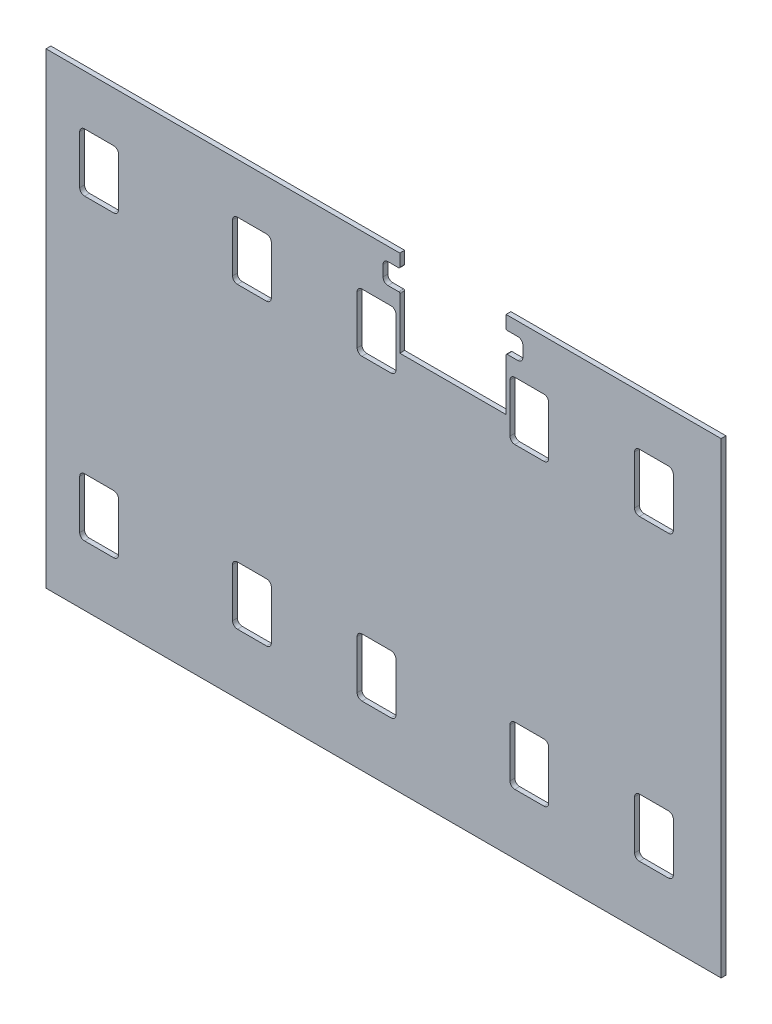
SolidWorks part; units mm, degrees
material "PP Film"
ref_plane "X-Y Datum" through (0, 0, 0) normal (0, 0, 1) x (1, 0, 0)
ref_plane "X-Z Datum" through (0, 0, 0) normal (0, 1, 0) x (1, 0, 0)
ref_plane "Y-Z Datum" through (0, 0, 0) normal (1, 0, 0) x (0, 0, -1)
sketch "Sketch1" plane through (0, 0, 0) normal (0, 0, 1) x (1, 0, 0)
  line L48 (-220.9897, 149.5877) -> (-220.9897, -156.2291)
  line L49 (-220.9897, -156.2291) -> (220.9897, -156.2291)
  line L50 (220.9897, -156.2291) -> (220.9897, 149.5877)
  line L51 (220.9897, 149.5877) -> (-220.9897, 149.5877)
extrude "Boss-Extrude1" add sketch "Sketch1" along normal blind 3.175 contours L50 L51 L48 L49 region at (0, -3.3207, 0)
sketch "Sketch2" plane through (0, 0, 3.175) normal (0, 0, 1) x (1, 0, 0)
  line L0 (-195.7605, 116.8) -> (-176.7105, 116.8) construction
  line L1 (-198.9355, 113.625) -> (-198.9355, 81.875) construction
  line L2 (-195.7605, 78.7) -> (-176.7105, 78.7) construction
  line L3 (-173.5355, 113.625) -> (-173.5355, 81.875) construction
  line L8 (-195.7605, 116.8) -> (-176.7105, 116.8)
  line L9 (-198.9355, 113.625) -> (-198.9355, 81.875)
  line L10 (-195.7605, 78.7) -> (-176.7105, 78.7)
  line L11 (-173.5355, 113.625) -> (-173.5355, 81.875)
  line L16 (-195.7605, -78.7) -> (-176.7105, -78.7) construction
  line L17 (-173.5355, -81.875) -> (-173.5355, -113.625) construction
  line L18 (-198.9355, -81.875) -> (-198.9355, -113.625) construction
  line L19 (-195.7605, -116.8) -> (-176.7105, -116.8) construction
  line L24 (-195.7605, -78.7) -> (-176.7105, -78.7)
  line L25 (-173.5355, -81.875) -> (-173.5355, -113.625)
  line L26 (-198.9355, -81.875) -> (-198.9355, -113.625)
  line L27 (-195.7605, -116.8) -> (-176.7105, -116.8)
  line L32 (-76.6655, -78.7) -> (-95.7155, -78.7) construction
  line L33 (-98.8905, -81.875) -> (-98.8905, -113.625) construction
  line L34 (-73.4905, -113.625) -> (-73.4905, -81.875) construction
  line L35 (-95.7155, -116.8) -> (-76.6655, -116.8) construction
  line L36 (-76.6655, -78.7) -> (-95.7155, -78.7)
  line L37 (-98.8905, -81.875) -> (-98.8905, -113.625)
  line L38 (-73.4905, -113.625) -> (-73.4905, -81.875)
  line L39 (-95.7155, -116.8) -> (-76.6655, -116.8)
  line L40 (-76.6655, 116.8) -> (-95.7155, 116.8) construction
  line L41 (-73.4905, 81.875) -> (-73.4905, 113.625) construction
  line L42 (-98.8905, 113.625) -> (-98.8905, 81.875) construction
  line L43 (-95.7155, 78.7) -> (-76.6655, 78.7) construction
  line L44 (-76.6655, 116.8) -> (-95.7155, 116.8)
  line L45 (-73.4905, 81.875) -> (-73.4905, 113.625)
  line L46 (-98.8905, 113.625) -> (-98.8905, 81.875)
  line L47 (-95.7155, 78.7) -> (-76.6655, 78.7)
  arc A0 (-173.5355, 113.625) -> (-176.7105, 116.8) centre (-176.7105, 113.625) ccw construction
  arc A1 (-195.7605, 116.8) -> (-198.9355, 113.625) centre (-195.7605, 113.625) ccw construction
  arc A2 (-198.9355, 81.875) -> (-195.7605, 78.7) centre (-195.7605, 81.875) ccw construction
  arc A3 (-176.7105, 78.7) -> (-173.5355, 81.875) centre (-176.7105, 81.875) ccw construction
  arc A8 (-173.5355, 113.625) -> (-176.7105, 116.8) centre (-176.7105, 113.625) ccw
  arc A9 (-195.7605, 116.8) -> (-198.9355, 113.625) centre (-195.7605, 113.625) ccw
  arc A10 (-198.9355, 81.875) -> (-195.7605, 78.7) centre (-195.7605, 81.875) ccw
  arc A11 (-176.7105, 78.7) -> (-173.5355, 81.875) centre (-176.7105, 81.875) ccw
  arc A16 (-195.7605, -78.7) -> (-198.9355, -81.875) centre (-195.7605, -81.875) ccw construction
  arc A17 (-173.5355, -81.875) -> (-176.7105, -78.7) centre (-176.7105, -81.875) ccw construction
  arc A18 (-176.7105, -116.8) -> (-173.5355, -113.625) centre (-176.7105, -113.625) ccw construction
  arc A19 (-198.9355, -113.625) -> (-195.7605, -116.8) centre (-195.7605, -113.625) ccw construction
  arc A24 (-195.7605, -78.7) -> (-198.9355, -81.875) centre (-195.7605, -81.875) ccw
  arc A25 (-173.5355, -81.875) -> (-176.7105, -78.7) centre (-176.7105, -81.875) ccw
  arc A26 (-176.7105, -116.8) -> (-173.5355, -113.625) centre (-176.7105, -113.625) ccw
  arc A27 (-198.9355, -113.625) -> (-195.7605, -116.8) centre (-195.7605, -113.625) ccw
  arc A32 (-73.4905, -81.875) -> (-76.6655, -78.7) centre (-76.6655, -81.875) ccw construction
  arc A33 (-95.7155, -78.7) -> (-98.8905, -81.875) centre (-95.7155, -81.875) ccw construction
  arc A34 (-76.6655, -116.8) -> (-73.4905, -113.625) centre (-76.6655, -113.625) ccw construction
  arc A35 (-98.8905, -113.625) -> (-95.7155, -116.8) centre (-95.7155, -113.625) ccw construction
  arc A36 (-73.4905, -81.875) -> (-76.6655, -78.7) centre (-76.6655, -81.875) ccw
  arc A37 (-95.7155, -78.7) -> (-98.8905, -81.875) centre (-95.7155, -81.875) ccw
  arc A38 (-76.6655, -116.8) -> (-73.4905, -113.625) centre (-76.6655, -113.625) ccw
  arc A39 (-98.8905, -113.625) -> (-95.7155, -116.8) centre (-95.7155, -113.625) ccw
  arc A40 (-73.4905, 113.625) -> (-76.6655, 116.8) centre (-76.6655, 113.625) ccw construction
  arc A41 (-95.7155, 116.8) -> (-98.8905, 113.625) centre (-95.7155, 113.625) ccw construction
  arc A42 (-76.6655, 78.7) -> (-73.4905, 81.875) centre (-76.6655, 81.875) ccw construction
  arc A43 (-98.8905, 81.875) -> (-95.7155, 78.7) centre (-95.7155, 81.875) ccw construction
  arc A44 (-73.4905, 113.625) -> (-76.6655, 116.8) centre (-76.6655, 113.625) ccw
  arc A45 (-95.7155, 116.8) -> (-98.8905, 113.625) centre (-95.7155, 113.625) ccw
  arc A46 (-76.6655, 78.7) -> (-73.4905, 81.875) centre (-76.6655, 81.875) ccw
  arc A47 (-98.8905, 81.875) -> (-95.7155, 78.7) centre (-95.7155, 81.875) ccw
extrude "Cut-Extrude1" cut sketch "Sketch2" against normal through all contours L26 A27 L27 A26 L25 A25 L24 A24 | L10 A11 L11 A8 L8 A9 L9 A10 region at (-186.2355, 97.75, 3.175) region at (-186.2355, -97.75, 3.175)
sketch "Sketch3" plane through (0, 0, 3.175) normal (0, 0, 1) x (1, 0, 0)
  line L5 (-176.7105, 116.8) -> (-195.7605, 116.8)
  line L6 (-173.5355, 81.875) -> (-173.5355, 113.625)
  line L7 (-195.7605, 78.7) -> (-176.7105, 78.7)
  line L13 (-198.9355, 113.625) -> (-198.9355, 81.875)
  line L14 (-176.7105, 116.8) -> (-195.7605, 116.8)
  line L15 (-173.5355, 81.875) -> (-173.5355, 113.625)
  line L21 (-195.7605, 78.7) -> (-176.7105, 78.7)
  line L22 (-198.9355, 113.625) -> (-198.9355, 81.875)
  line L23 (-173.5355, -113.625) -> (-173.5355, -81.875)
  line L29 (-195.7605, -116.8) -> (-176.7105, -116.8)
  line L30 (-198.9355, -81.875) -> (-198.9355, -113.625)
  line L31 (-176.7105, -78.7) -> (-195.7605, -78.7)
  line L36 (-173.5355, -113.625) -> (-173.5355, -81.875)
  line L37 (-195.7605, -116.8) -> (-176.7105, -116.8)
  line L38 (-198.9355, -81.875) -> (-198.9355, -113.625)
  line L39 (-176.7105, -78.7) -> (-195.7605, -78.7)
  line L40 (-76.6655, 116.8) -> (-95.7155, 116.8)
  line L41 (-98.8905, 113.625) -> (-98.8905, 81.875)
  line L42 (-95.7155, 78.7) -> (-76.6655, 78.7)
  line L43 (-73.4905, 81.875) -> (-73.4905, 113.625)
  line L44 (-76.6655, 116.8) -> (-95.7155, 116.8)
  line L45 (-98.8905, 113.625) -> (-98.8905, 81.875)
  line L46 (-95.7155, 78.7) -> (-76.6655, 78.7)
  line L47 (-73.4905, 81.875) -> (-73.4905, 113.625)
  line L48 (-95.7155, -116.8) -> (-76.6655, -116.8)
  line L49 (-98.8905, -81.875) -> (-98.8905, -113.625)
  line L50 (-76.6655, -78.7) -> (-95.7155, -78.7)
  line L51 (-73.4905, -113.625) -> (-73.4905, -81.875)
  line L52 (-95.7155, -116.8) -> (-76.6655, -116.8)
  line L53 (-98.8905, -81.875) -> (-98.8905, -113.625)
  line L54 (-76.6655, -78.7) -> (-95.7155, -78.7)
  line L55 (-73.4905, -113.625) -> (-73.4905, -81.875)
  arc A36 (-173.5355, 113.625) -> (-176.7105, 116.8) centre (-176.7105, 113.625) ccw
  arc A37 (-176.7105, 78.7) -> (-173.5355, 81.875) centre (-176.7105, 81.875) ccw
  arc A38 (-198.9355, 81.875) -> (-195.7605, 78.7) centre (-195.7605, 81.875) ccw
  arc A39 (-195.7605, 116.8) -> (-198.9355, 113.625) centre (-195.7605, 113.625) ccw
  arc A40 (-173.5355, 113.625) -> (-176.7105, 116.8) centre (-176.7105, 113.625) ccw
  arc A41 (-176.7105, 78.7) -> (-173.5355, 81.875) centre (-176.7105, 81.875) ccw
  arc A42 (-198.9355, 81.875) -> (-195.7605, 78.7) centre (-195.7605, 81.875) ccw
  arc A43 (-195.7605, 116.8) -> (-198.9355, 113.625) centre (-195.7605, 113.625) ccw
  arc A44 (-176.7105, -116.8) -> (-173.5355, -113.625) centre (-176.7105, -113.625) ccw
  arc A45 (-198.9355, -113.625) -> (-195.7605, -116.8) centre (-195.7605, -113.625) ccw
  arc A46 (-195.7605, -78.7) -> (-198.9355, -81.875) centre (-195.7605, -81.875) ccw
  arc A47 (-173.5355, -81.875) -> (-176.7105, -78.7) centre (-176.7105, -81.875) ccw
  arc A48 (-176.7105, -116.8) -> (-173.5355, -113.625) centre (-176.7105, -113.625) ccw
  arc A49 (-198.9355, -113.625) -> (-195.7605, -116.8) centre (-195.7605, -113.625) ccw
  arc A50 (-195.7605, -78.7) -> (-198.9355, -81.875) centre (-195.7605, -81.875) ccw
  arc A51 (-173.5355, -81.875) -> (-176.7105, -78.7) centre (-176.7105, -81.875) ccw
  arc A52 (-95.7155, 116.8) -> (-98.8905, 113.625) centre (-95.7155, 113.625) ccw
  arc A53 (-98.8905, 81.875) -> (-95.7155, 78.7) centre (-95.7155, 81.875) ccw
  arc A54 (-76.6655, 78.7) -> (-73.4905, 81.875) centre (-76.6655, 81.875) ccw
  arc A55 (-73.4905, 113.625) -> (-76.6655, 116.8) centre (-76.6655, 113.625) ccw
  arc A56 (-95.7155, 116.8) -> (-98.8905, 113.625) centre (-95.7155, 113.625) ccw
  arc A57 (-98.8905, 81.875) -> (-95.7155, 78.7) centre (-95.7155, 81.875) ccw
  arc A58 (-76.6655, 78.7) -> (-73.4905, 81.875) centre (-76.6655, 81.875) ccw
  arc A59 (-73.4905, 113.625) -> (-76.6655, 116.8) centre (-76.6655, 113.625) ccw
  arc A60 (-76.6655, -116.8) -> (-73.4905, -113.625) centre (-76.6655, -113.625) ccw
  arc A61 (-98.8905, -113.625) -> (-95.7155, -116.8) centre (-95.7155, -113.625) ccw
  arc A62 (-95.7155, -78.7) -> (-98.8905, -81.875) centre (-95.7155, -81.875) ccw
  arc A63 (-73.4905, -81.875) -> (-76.6655, -78.7) centre (-76.6655, -81.875) ccw
  arc A64 (-76.6655, -116.8) -> (-73.4905, -113.625) centre (-76.6655, -113.625) ccw
  arc A65 (-98.8905, -113.625) -> (-95.7155, -116.8) centre (-95.7155, -113.625) ccw
  arc A66 (-95.7155, -78.7) -> (-98.8905, -81.875) centre (-95.7155, -81.875) ccw
  arc A67 (-73.4905, -81.875) -> (-76.6655, -78.7) centre (-76.6655, -81.875) ccw
  dimension "D1" = 0
  dimension "D2" = 0
  dimension "D3" = 0
  dimension "D4" = 0
extrude "Cut-Extrude2" cut sketch "Sketch3" against normal through all contours L55 A67 L54 A66 L53 A65 L52 A64 | L47 A59 L44 A56 L45 A57 L46 A58 region at (-86.1905, 97.75, 3.175) region at (-86.1905, -97.75, 3.175)
pattern_linear "LPattern1" count 3 spacing 181.614 along (1, 0, 0) of "Cut-Extrude1"
pattern_linear "LPattern2" count 2 spacing 181.614 along (1, 0, 0) of "Cut-Extrude2"
sketch "Sketch4" plane through (0, 0, 3.175) normal (0, 0, 1) x (1, 0, 0)
  line L0 (78.901, 149.0877) -> (75.901, 149.0877) construction
  line L1 (75.901, 149.0877) -> (75.901, 94.0877) construction
  line L2 (75.901, 94.0877) -> (78.901, 94.0877) construction
  line L3 (78.901, 94.0877) -> (78.901, 149.0877) construction
  line L4 (9.901, 139.5877) -> (2.901, 139.5877)
  line L5 (0.901, 137.5877) -> (0.901, 130.5877)
  line L6 (2.901, 128.5877) -> (9.901, 128.5877)
  line L7 (11.901, 126.5877) -> (11.901, 141.5877)
  line L8 (9.901, 139.5877) -> (2.901, 139.5877) construction
  line L9 (0.901, 137.5877) -> (0.901, 130.5877) construction
  line L10 (2.901, 128.5877) -> (9.901, 128.5877) construction
  line L11 (11.901, 126.5877) -> (11.901, 141.5877) construction
  line L12 (89.901, 130.5877) -> (89.901, 137.5877)
  line L13 (87.901, 139.5877) -> (80.901, 139.5877)
  line L14 (78.901, 141.5877) -> (78.901, 126.5877)
  line L15 (80.901, 128.5877) -> (87.901, 128.5877)
  line L16 (89.901, 130.5877) -> (89.901, 137.5877) construction
  line L17 (87.901, 139.5877) -> (80.901, 139.5877) construction
  line L18 (78.901, 141.5877) -> (78.901, 126.5877) construction
  line L19 (80.901, 128.5877) -> (87.901, 128.5877) construction
  line L20 (11.901, 94.0877) -> (14.901, 94.0877) construction
  line L21 (14.901, 94.0877) -> (14.901, 149.0877) construction
  line L23 (11.901, 149.0877) -> (11.901, 94.0877) construction
  line L24 (78.901, 149.0877) -> (75.901, 149.0877) construction
  line L25 (75.901, 149.0877) -> (75.901, 94.0877) construction
  line L26 (75.901, 94.0877) -> (78.901, 94.0877) construction
  line L27 (78.901, 94.0877) -> (78.901, 149.0877) construction
  line L28 (11.901, 94.0877) -> (14.901, 94.0877) construction
  line L29 (14.901, 94.0877) -> (14.901, 149.0877) construction
  line L31 (11.901, 149.0877) -> (11.901, 94.0877) construction
  line L32 (14.901, 94.0877) -> (75.901, 94.0877) construction
  line L33 (11.901, 149.0877) -> (11.901, 149.5877) construction
  line L34 (220.9897, 149.5877) -> (-220.9897, 149.5877) construction
  line L35 (78.901, 149.0877) -> (78.901, 149.5877) construction
  line L36 (220.9897, 149.5877) -> (-220.9897, 149.5877) construction
  line L37 (220.9897, 149.5877) -> (-220.9897, 149.5877) construction
  line L38 (9.901, 140.8577) -> (2.901, 140.8577)
  line L39 (-0.369, 137.5877) -> (-0.369, 130.5877)
  line L40 (2.901, 127.3177) -> (9.901, 127.3177)
  line L41 (10.631, 149.5877) -> (10.631, 92.8177)
  line L42 (10.631, 92.8177) -> (14.901, 92.8177)
  line L43 (14.901, 92.8177) -> (75.901, 92.8177)
  line L44 (75.901, 92.8177) -> (80.171, 92.8177)
  line L45 (80.171, 92.8177) -> (80.171, 149.5877)
  line L46 (80.171, 127.3177) -> (87.901, 127.3177)
  line L47 (91.171, 130.5877) -> (91.171, 137.5877)
  line L48 (87.901, 140.8577) -> (80.171, 140.8577)
  line L49 (10.631, 149.0877) -> (10.631, 92.8177) construction
  line L50 (80.171, 92.8177) -> (80.171, 149.0877) construction
  line L51 (87.901, 140.8577) -> (80.901, 140.8577) construction
  line L52 (80.901, 127.3177) -> (87.901, 127.3177) construction
  line L53 (10.631, 149.5877) -> (80.171, 149.5877)
  arc A0 (9.901, 140.8577) -> (10.631, 141.5877) centre (9.901, 141.5877) ccw
  arc A1 (2.901, 140.8577) -> (-0.369, 137.5877) centre (2.901, 137.5877) ccw
  arc A2 (-0.369, 130.5877) -> (2.901, 127.3177) centre (2.901, 130.5877) ccw
  arc A3 (10.631, 126.5877) -> (9.901, 127.3177) centre (9.901, 126.5877) ccw
  arc A4 (2.901, 139.5877) -> (0.901, 137.5877) centre (2.901, 137.5877) ccw
  arc A5 (0.901, 130.5877) -> (2.901, 128.5877) centre (2.901, 130.5877) ccw
  arc A6 (11.901, 126.5877) -> (9.901, 128.5877) centre (9.901, 126.5877) ccw
  arc A7 (9.901, 139.5877) -> (11.901, 141.5877) centre (9.901, 141.5877) ccw
  arc A8 (2.901, 139.5877) -> (0.901, 137.5877) centre (2.901, 137.5877) ccw construction
  arc A9 (0.901, 130.5877) -> (2.901, 128.5877) centre (2.901, 130.5877) ccw construction
  arc A10 (11.901, 126.5877) -> (9.901, 128.5877) centre (9.901, 126.5877) ccw construction
  arc A11 (9.901, 139.5877) -> (11.901, 141.5877) centre (9.901, 141.5877) ccw construction
  arc A12 (89.901, 137.5877) -> (87.901, 139.5877) centre (87.901, 137.5877) ccw
  arc A13 (78.901, 141.5877) -> (80.901, 139.5877) centre (80.901, 141.5877) ccw
  arc A14 (80.901, 128.5877) -> (78.901, 126.5877) centre (80.901, 126.5877) ccw
  arc A15 (87.901, 128.5877) -> (89.901, 130.5877) centre (87.901, 130.5877) ccw
  arc A16 (89.901, 137.5877) -> (87.901, 139.5877) centre (87.901, 137.5877) ccw construction
  arc A17 (78.901, 141.5877) -> (80.901, 139.5877) centre (80.901, 141.5877) ccw construction
  arc A18 (80.901, 128.5877) -> (78.901, 126.5877) centre (80.901, 126.5877) ccw construction
  arc A19 (87.901, 128.5877) -> (89.901, 130.5877) centre (87.901, 130.5877) ccw construction
  arc A20 (87.901, 127.3177) -> (91.171, 130.5877) centre (87.901, 130.5877) ccw
  arc A21 (91.171, 137.5877) -> (87.901, 140.8577) centre (87.901, 137.5877) ccw
  arc A22 (80.171, 141.5877) -> (80.901, 140.8577) centre (80.901, 141.5877) ccw
  arc A23 (80.901, 127.3177) -> (80.171, 126.5877) centre (80.901, 126.5877) ccw
  point P64 (80.1327, 149.5877)
  dimension "D1" = 0
  dimension "D2" = 0
  dimension "D3" = 1.27
  dimension "D4" = 1.27
extrude "Cut-Extrude3" cut sketch "Sketch4" against normal through all contours L35 L37 L33 L29 L32 L25 L24 | L31 L11 L28 L29 | A11 L8 A8 L9 A9 L10 A10 L11 | L26 L27 L18 L24 L25 | L19 A19 L16 A16 L17 A17 L18 A18 | L53 L41 L42 L43 L44 L45 | A3 L41 A0 L38 A1 L39 A2 L40 | L47 A21 L48 L45 L46 A20 | A23 L46 L45 | A22 L45 L48 region at (6.401, 139.7737, 3.175) region at (45.401, 121.0999, 3.175) region at (80.3341, 141.0208, 3.175) region at (80.536, 140.6833, 3.175) region at (80.3341, 127.1547, 3.175) body kept at (220.9897, 149.5877, 0)
